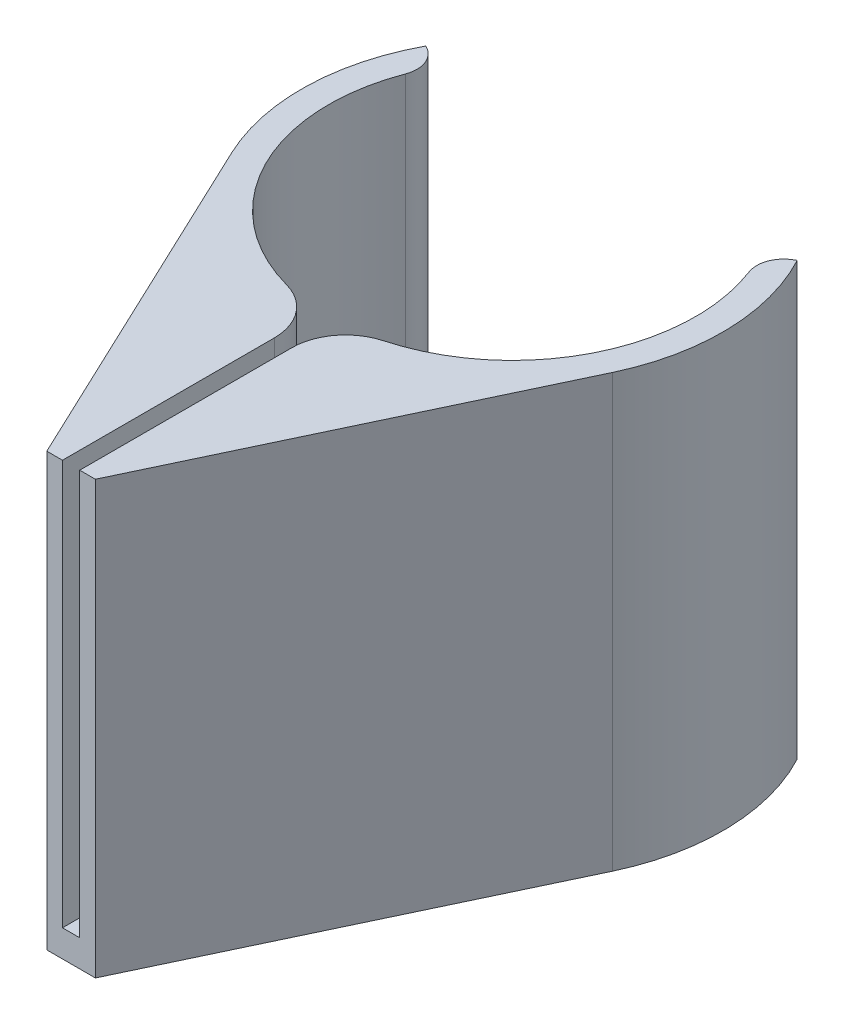
SolidWorks part; units mm, degrees
ref_plane "Front Plane" through (0, 0, 0) normal (0, 0, 1) x (1, 0, 0)
ref_plane "Top Plane" through (0, 0, 0) normal (0, 1, 0) x (1, 0, 0)
ref_plane "Right Plane" through (0, 0, 0) normal (1, 0, 0) x (0, 0, -1)
sketch "body tube profile" plane through (0, 0, 0) normal (0, 1, 0) x (1, 0, 0)
  circle A0 centre (0, 0) radius 34
  dimension "D1" = 68
sketch "Sketch2" plane through (0, 0, 0) normal (0, 1, 0) x (1, 0, 0)
  line L1 (0, 0) -> (0, -34) construction
  line L2 (-35.2539, -16.6782) -> (-4.5, -81.685)
  line L13 (29.4449, 17) -> (33.775, 19.5) construction
  line L14 (-4.5, -81.685) -> (4.5, -81.685)
  line L15 (30.05, 15.906) -> (34.3826, 18.4074)
  line L16 (0, -55) -> (0, 55) construction
  line L17 (-30.05, 15.906) -> (-34.3826, 18.4074)
  line L18 (4.5, -81.685) -> (35.2539, -16.6782)
  circle A0 centre (0, 0) radius 39 construction
  circle A3 centre (0, 0) radius 34 construction
  arc A4 (-30.05, 15.906) -> (30.05, 15.906) centre (0, 0) ccw
  arc A6 (-34.3826, 18.4074) -> (-35.2539, -16.6782) centre (0, 0) ccw
  circle A7 centre (0, 0) radius 34 construction
  arc A8 (35.2539, -16.6782) -> (34.3826, 18.4074) centre (0, 0) ccw
  point P10 (0, -81.685)
  dimension "D2" = 9
  dimension "D3" = 120
  dimension "D4" = 81.685
  dimension "D5" = 2.5
  dimension "D6" = 5
  dimension "D1" = 5
extrude "Fin slot extrude" add sketch "Sketch2" along normal blind 80 contours L17 region at (0, 0, 39.8733)
sketch "Sketch3" plane through (0, 80, 0) normal (0, 1, 0) x (1, 0, 0)
  line L0 (0, -81.685) -> (0, -34) construction
  line L1 (-4.5, -81.685) -> (4.5, -81.685) construction
  line L2 (1.6, -81.685) -> (1.6, -33.9623)
  line L3 (-1.6, -81.685) -> (-1.6, -33.9623)
  line L4 (-1.6, -81.685) -> (1.6, -81.685)
  arc A0 (-30.05, 15.906) -> (30.05, 15.906) centre (0, 0) ccw construction
  arc A1 (-1.6, -33.9623) -> (1.6, -33.9623) centre (0, 0) ccw
  dimension "D1" = 1.6
extrude "Fin slot" cut sketch "Sketch3" against normal offset from surface (75 mm away) 5 up to face at (0, 0, 22.2248)
fillet "Fillet1" radius 10 3 edges at (0, 5, 34) (1.6, 42.5, 33.9623) (-1.6, 42.5, 33.9623)
fillet "Fillet2" radius 5 2 edges at (-30.05, 40, -15.906) (30.05, 40, -15.906)
